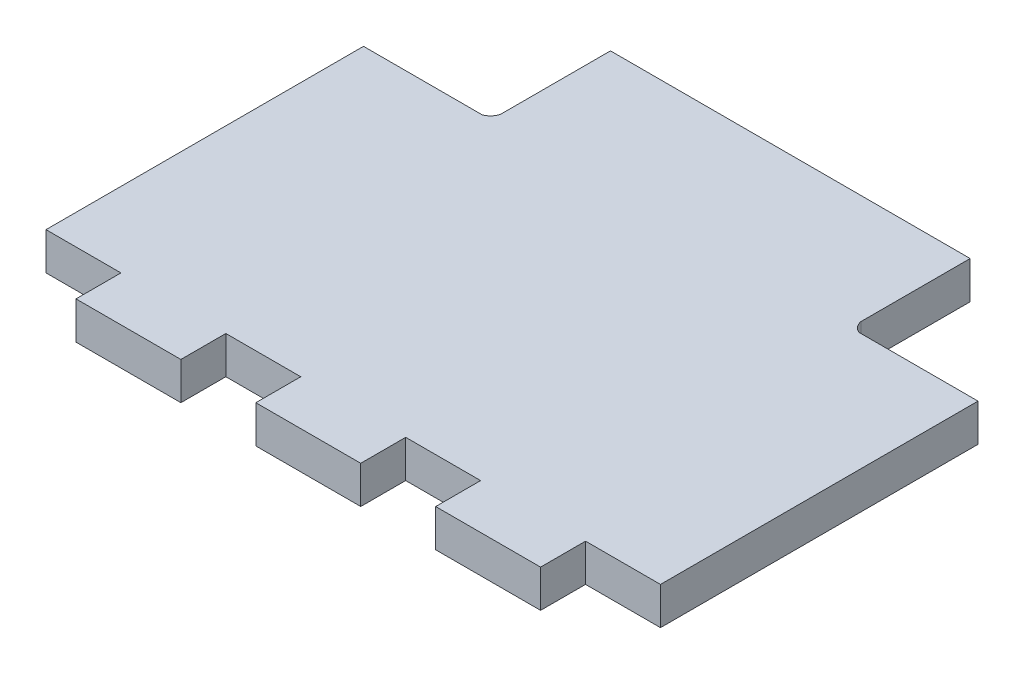
SolidWorks part; units mm, degrees
ref_plane "Alzado" through (0, 0, 0) normal (0, 0, 1) x (1, 0, 0)
ref_plane "Planta" through (0, 0, 0) normal (0, 1, 0) x (1, 0, 0)
ref_plane "Vista lateral" through (0, 0, 0) normal (1, 0, 0) x (0, 0, -1)
sketch "Croquis1" plane through (0, 0, 0) normal (0, 1, 0) x (1, 0, 0)
  line L0 (-60.9148, -22.524) -> (-40.9148, -22.524)
  line L1 (103.0852, 62.2178) -> (71.3494, 62.2178)
  line L2 (-60.9148, 62.2178) -> (-60.9148, -22.524)
  line L3 (-12.9148, -22.524) -> (7.0852, -22.524)
  line L4 (103.0852, 62.2178) -> (103.0852, -22.524)
  line L5 (-60.9148, 62.2178) -> (-29.2217, 62.2178)
  line L6 (-26.9148, 94.1277) -> (69.0852, 94.1277)
  line L7 (69.0852, 64.9385) -> (69.0852, 94.1277)
  line L8 (-26.9148, 64.8488) -> (-26.9148, 94.1277)
  line L10 (-40.9148, -22.524) -> (-40.9148, -34.524)
  line L11 (-40.9148, -34.524) -> (-12.9148, -34.524)
  line L12 (-12.9148, -22.524) -> (-12.9148, -34.524)
  line L14 (7.0852, -22.524) -> (7.0852, -34.524)
  line L15 (7.0852, -34.524) -> (35.0852, -34.524)
  line L16 (35.0852, -22.524) -> (35.0852, -34.524)
  line L18 (55.0852, -22.524) -> (55.0852, -34.524)
  line L19 (55.0852, -34.524) -> (83.0852, -34.524)
  line L20 (83.0852, -22.524) -> (83.0852, -34.524)
  line L21 (35.0852, -22.524) -> (55.0852, -22.524)
  line L22 (83.0852, -22.524) -> (103.0852, -22.524)
  arc A0 (69.0852, 64.9385) -> (71.3494, 62.2178) centre (72.7148, 65.6566) ccw
  arc A1 (-29.2217, 62.2178) -> (-26.9148, 64.8488) centre (-30.5196, 65.6826) ccw
  circle A4 centre (0, 35.3805) radius 5
  circle A5 centre (40, 35.3805) radius 5
  dimension "D10" = 20
  dimension "D14" = 40
  dimension "D11" = 20
  dimension "D12" = 20
  dimension "D13" = 20
extrude "Saliente-Extruir1" add sketch "Croquis1" along normal blind 10 contours L2 L0 L10 L11 L12 L3 L14 L15 L16 L21 L18 L19 L20 L22 L4 L1 A0 L7 L6 L8 A1 L5
extrude "Cortar-Extruir1" cut sketch "Croquis1<10>" along normal blind 6 contours A4 | A5
sketch "Croquis1<10>" plane through (0, 0, 0) normal (0, 1, 0) x (1, 0, 0) same geometry as "Croquis1"
extrude "Cortar-Extruir3" cut sketch "Croquis1<11>" along normal through all rebuild error yes
sketch "Croquis1<11>" plane through (0, 0, 0) normal (0, 1, 0) x (1, 0, 0) same geometry as "Croquis1"
